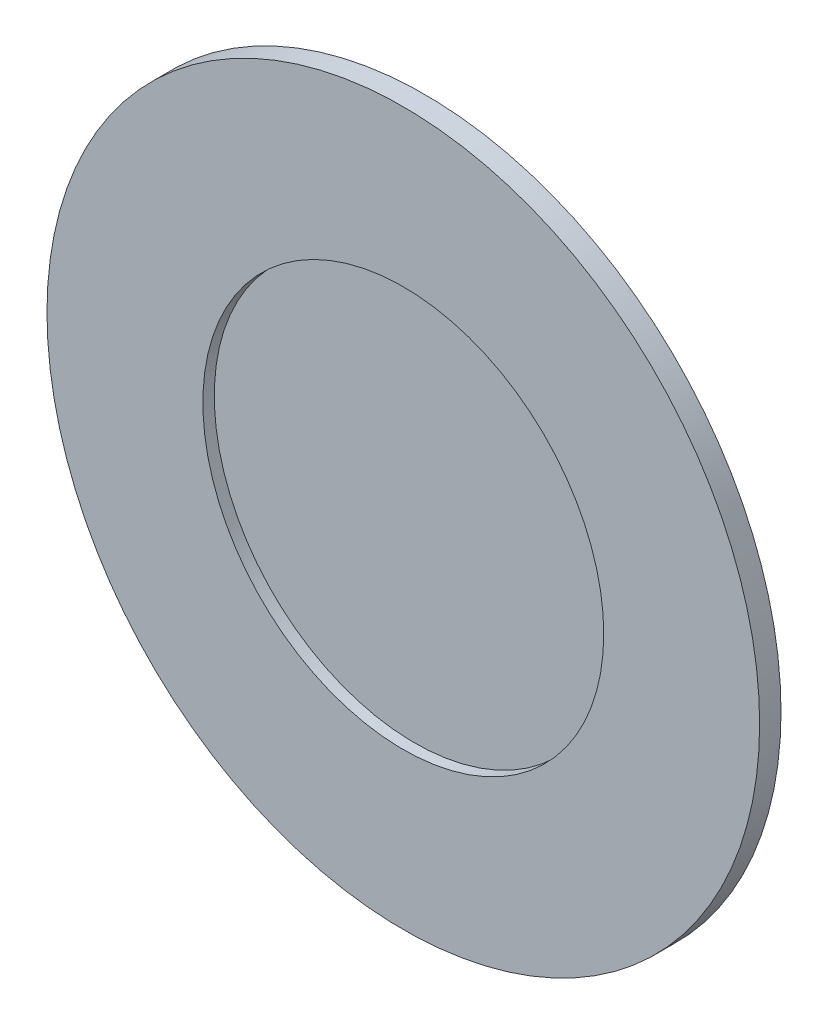
SolidWorks part; units mm, degrees
material "PTFE (general)"
ref_plane "Front Plane" through (0, 0, 0) normal (0, 0, 1) x (1, 0, 0)
ref_plane "Top Plane" through (0, 0, 0) normal (0, 1, 0) x (1, 0, 0)
ref_plane "Right Plane" through (0, 0, 0) normal (1, 0, 0) x (0, 0, -1)
sketch "Sketch1" plane through (0, 0, 0) normal (0, 0, 1) x (1, 0, 0)
  circle A0 centre (0, 0) radius 3.5719
  circle A1 centre (0, 0) radius 6.35
  dimension "D1" = 12.7
  dimension "D2" = 7.1437
extrude "Boss-Extrude1" add sketch "Sketch1" along normal blind 0.381 contours A1
extrude "Cut-Extrude2" cut sketch "Sketch1<3>" against normal offset from surface (0.2032 mm away) 0.1778 from surface contours A0 up to face at (6.35, 0, 0) starting at face at (6.35, 0, 0.381)
sketch "Sketch1<3>" plane through (0, 0, 0) normal (0, 0, 1) x (1, 0, 0) same geometry as "Sketch1"
equation "\"D2@Sketch1\"=9/32"
